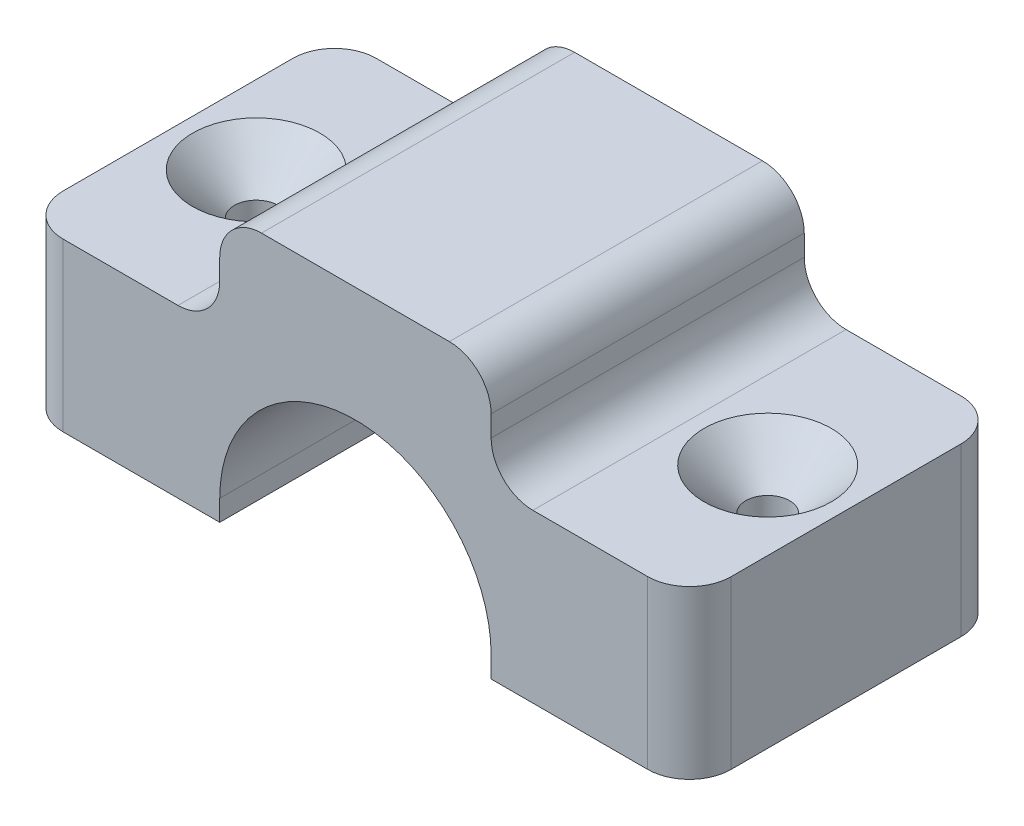
SolidWorks part; units mm, degrees
ref_plane "Front Plane" through (0, 0, 0) normal (0, 0, 1) x (1, 0, 0)
ref_plane "Top Plane" through (0, 0, 0) normal (0, 1, 0) x (1, 0, 0)
ref_plane "Right Plane" through (0, 0, 0) normal (1, 0, 0) x (0, 0, -1)
sketch "Sketch1" plane through (0, 0, 0) normal (0, 0, 1) x (1, 0, 0)
  line L0 (-16, 0) -> (-6.5, 0)
  line L1 (16, -12) -> (-16, -12)
  line L2 (16, -12) -> (16, 12)
  line L3 (16, 12) -> (-16, 12)
  line L4 (-16, -12) -> (-16, 12)
  line L5 (0, 12) -> (0, -12) construction
  line L6 (16, 0) -> (-16, 0) construction
  line L7 (6.5, 0) -> (16, 0)
  circle A0 centre (0, 0) radius 6.5
  point P0 (0, 0)
  dimension "D3" = 13
  dimension "D1" = 32
  dimension "D2" = 24
extrude "Boss-Extrude1" add sketch "Sketch1" along normal blind 15 contours A0 L7 L2 L3 L4 L0 region at (0, 6.6772, 0)
sketch "Sketch2" plane through (0, 0, 0) normal (0, -1, 0) x (1, 0, 0)
  line L0 (-16, 15) -> (16, 15) construction
  line L1 (0, 15) -> (0, 0) construction
  line L2 (0, 0) -> (-16, 0) construction
  line L3 (-12.25, 0) -> (-12.25, 15) construction
  line L4 (-16, 0) -> (-6.5, 0)
  line L5 (-6.5, 0) -> (-6.5, 15)
  line L6 (-6.5, 15) -> (-16, 15)
  line L7 (-16, 15) -> (-16, 0)
  line L8 (-16, 0) -> (-6.5, 0)
  line L9 (-6.5, 0) -> (-6.5, 15)
  line L10 (-6.5, 15) -> (-16, 15)
  line L11 (-16, 15) -> (-16, 0)
  line L12 (6.5, 0) -> (16, 0)
  line L13 (16, 0) -> (16, 15)
  line L14 (16, 15) -> (6.5, 15)
  line L15 (6.5, 15) -> (6.5, 0)
  line L16 (6.5, 0) -> (16, 0)
  line L17 (16, 0) -> (16, 15)
  line L18 (16, 15) -> (6.5, 15)
  line L19 (6.5, 15) -> (6.5, 0)
  circle A0 centre (-12.25, 7.5) radius 1.05
  circle A1 centre (12.25, 7.5) radius 1.05
  dimension "D4" = 2.1
  dimension "D3" = 3.75
  dimension "D1" = 0
  dimension "D2" = 0
extrude "Cut-Extrude1" cut sketch "Sketch2" along normal blind 19 and the other way through all from surface contours A1 | A0 starting at face at (0, 12, 7.5)
fillet "Fillet1" radius 2 4 edges at (-16, 6, 15) (16, 6, 15) (16, 6, 0) (-16, 6, 0)
sketch "Sketch3" plane through (0, 0, 0) normal (0, -1, 0) x (1, 0, 0)
  line L4 (-14, 0) -> (-6.5, 0)
  line L5 (-6.5, 0) -> (-6.5, 15)
  line L6 (-6.5, 15) -> (-14, 15)
  line L7 (-16, 13) -> (-16, 2)
  line L8 (-14, 0) -> (-6.5, 0)
  line L9 (-6.5, 0) -> (-6.5, 15)
  line L10 (-6.5, 15) -> (-14, 15)
  line L11 (-16, 13) -> (-16, 2)
  line L12 (6.5, 0) -> (14, 0)
  line L13 (16, 2) -> (16, 13)
  line L14 (14, 15) -> (6.5, 15)
  line L15 (6.5, 15) -> (6.5, 0)
  line L16 (6.5, 0) -> (14, 0)
  line L17 (16, 2) -> (16, 13)
  line L18 (14, 15) -> (6.5, 15)
  line L19 (6.5, 15) -> (6.5, 0)
  circle A0 centre (12.25, 7.5) radius 1.05 construction
  circle A1 centre (-12.25, 7.5) radius 1.05 construction
  circle A2 centre (12.25, 7.5) radius 1.05
  circle A3 centre (-12.25, 7.5) radius 1.05
  arc A6 (-14, 15) -> (-16, 13) centre (-14, 13) ccw
  arc A7 (-14, 15) -> (-16, 13) centre (-14, 13) ccw
  arc A8 (-16, 2) -> (-14, 0) centre (-14, 2) ccw
  arc A9 (-16, 2) -> (-14, 0) centre (-14, 2) ccw
  arc A10 (16, 13) -> (14, 15) centre (14, 13) ccw
  arc A11 (16, 13) -> (14, 15) centre (14, 13) ccw
  arc A12 (14, 0) -> (16, 2) centre (14, 2) ccw
  arc A13 (14, 0) -> (16, 2) centre (14, 2) ccw
  dimension "D1" = 0
  dimension "D2" = 0
extrude "Boss-Extrude2" add sketch "Sketch3" along normal blind 1
extrude "Cut-Extrude2" cut sketch "Sketch2<3>" along normal blind 5 from surface starting at face at (13.3, 12, 7.5)
sketch "Sketch2<3>" plane through (0, 0, 0) normal (0, -1, 0) x (1, 0, 0) same geometry as "Sketch2"
fillet "Fillet2" radius 2 4 edges at (6.5, 12, 7.5) (-6.5, 12, 7.5) (-6.5, 7, 7.5) (6.5, 7, 7.5)
chamfer "Chamfer1" distance 2 angle 45 2 edges at (13.3, 7, 7.5) (-11.2, 7, 7.5)
